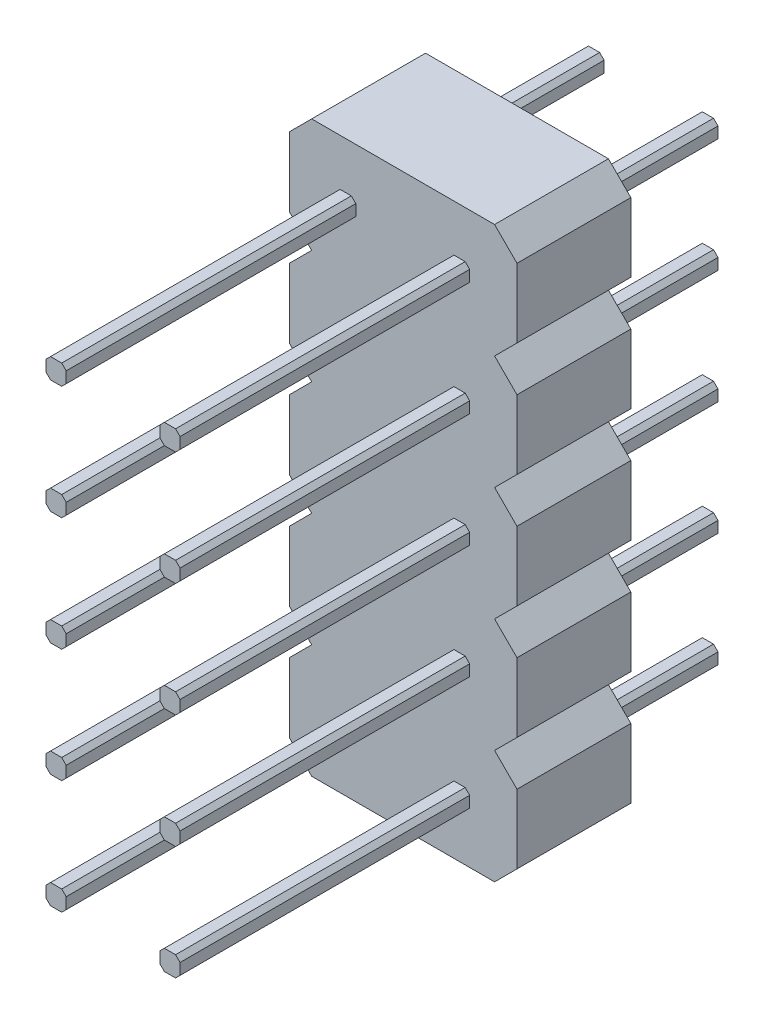
SolidWorks part; units mm, degrees
ref_plane "Front Plane" through (0, 0, 0) normal (0, 0, 1) x (1, 0, 0)
ref_plane "Top Plane" through (0, 0, 0) normal (0, 1, 0) x (1, 0, 0)
ref_plane "Right Plane" through (0, 0, 0) normal (1, 0, 0) x (0, 0, -1)
sketch "Sketch1" plane through (0, 0, 0) normal (0, 0, 1) x (1, 0, 0)
  line L0 (-0.125, 0.225) -> (-0.225, 0.125)
  line L1 (0.125, -0.225) -> (-0.125, -0.225)
  line L2 (0.225, -0.125) -> (0.225, 0.125)
  line L3 (0.125, 0.225) -> (-0.125, 0.225)
  line L4 (-0.225, -0.125) -> (-0.225, 0.125)
  line L5 (0.225, -0.225) -> (-0.225, 0.225) construction
  line L6 (0.225, 0.225) -> (-0.225, -0.225) construction
  line L7 (0.225, 0.125) -> (0.125, 0.225)
  line L8 (0.225, -0.125) -> (0.125, -0.225)
  line L9 (-0.125, -0.225) -> (-0.225, -0.125)
  point P0 (0, 0)
  dimension "D1" = 0.45
extrude "Boss-Extrude1" add sketch "Sketch1" along normal blind 12
pattern_linear "LPattern1" count 2 spacing 2.54 along (1, 0, 0) of bodies 101
ref_plane "Plane1" through (0, 0, 3) normal (0, 0, -1) x (-1, 0, 0)
sketch "Sketch3" plane through (0, 0, 3) normal (0, 0, -1) x (-1, 0, 0)
  line L0 (-2.7874, 0) -> (0.225, 0) construction
  line L1 (0.225, 0.125) -> (0.225, -0.125) construction
  line L2 (-3.3212, -1.27) -> (-3.8212, -0.77)
  line L3 (0.7588, -1.27) -> (-3.3212, -1.27)
  line L4 (1.2588, -0.77) -> (1.2588, 0.77)
  line L5 (0.7588, 1.27) -> (-3.3212, 1.27)
  line L6 (-3.8212, -0.77) -> (-3.8212, 0.77)
  line L7 (1.2588, -1.27) -> (-3.8212, 1.27) construction
  line L8 (1.2588, 1.27) -> (-3.8212, -1.27) construction
  line L9 (1.2588, -0.77) -> (0.7588, -1.27)
  line L10 (1.2588, 0.77) -> (0.7588, 1.27)
  line L11 (-3.3212, 1.27) -> (-3.8212, 0.77)
  point P4 (-1.2812, 0)
  dimension "D1" = 5.08
  dimension "D2" = 2.54
extrude "Boss-Extrude2" add sketch "Sketch3" against normal blind 2.54
pattern_linear "LPattern2" count 5 spacing 2.54 along (0, 1, 0) of bodies 103
combine bodies "Combine1" operation type add bodies to combine 103 104 105 106 107
